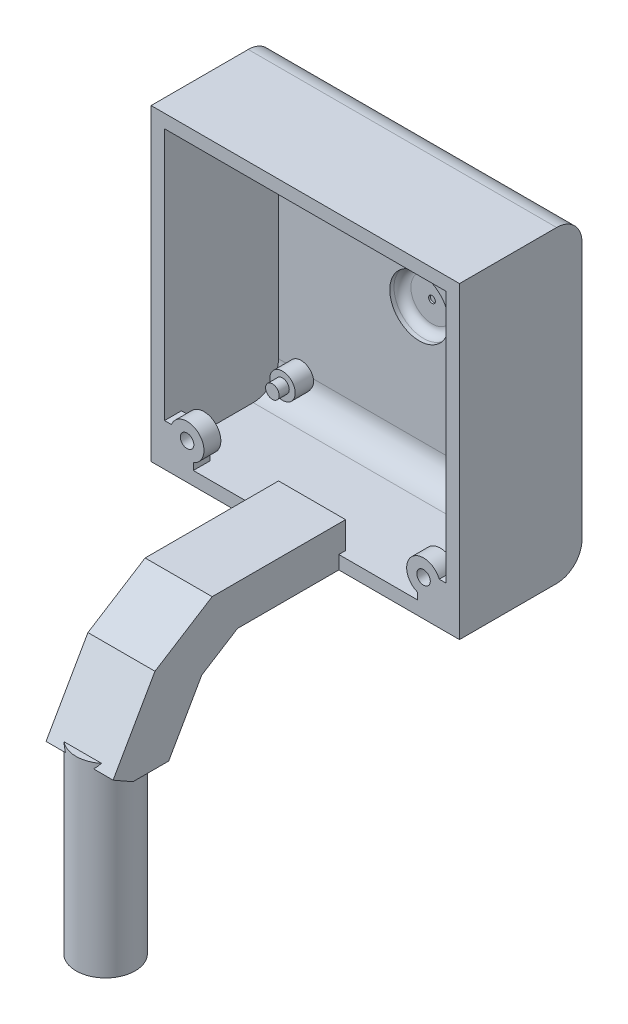
SolidWorks part; units mm, degrees
ref_plane "Front Plane" through (0, 0, 0) normal (0, 0, 1) x (1, 0, 0)
ref_plane "Top Plane" through (0, 0, 0) normal (0, 1, 0) x (1, 0, 0)
ref_plane "Right Plane" through (0, 0, 0) normal (1, 0, 0) x (0, 0, -1)
sketch "Sketch1" plane through (0, 0, 0) normal (0, 0, 1) x (1, 0, 0)
  line L0 (0, 0) -> (0, -36.5125)
  line L1 (0, -36.5125) -> (36.5125, -36.5125)
  line L2 (36.5125, -36.5125) -> (36.5125, 0)
  line L3 (36.5125, 0) -> (0, 0)
  dimension "D1" = 36.5125
extrude "Extrude1" add sketch "Sketch1" along normal blind 1
sketch "Sketch2" plane through (0, 0, 1) normal (0, 0, 1) x (1, 0, 0)
  line L0 (1.5875, -1.5875) -> (34.925, -1.5875)
  line L3 (34.925, -34.925) -> (34.925, -1.5875)
  line L4 (1.5875, -34.925) -> (1.5875, -1.5875)
  line L5 (34.925, -34.925) -> (1.5875, -34.925)
  line L6 (0, 0) -> (36.5125, 0)
  line L7 (36.5125, -36.5125) -> (36.5125, 0) construction
  line L8 (36.5125, 0) -> (0, 0) construction
  line L9 (36.5125, 0) -> (36.5125, -36.5125)
  line L10 (0, -36.5125) -> (36.5125, -36.5125) construction
  line L11 (36.5125, -36.5125) -> (0, -36.5125)
  line L12 (0, 0) -> (0, -36.5125) construction
  line L13 (0, -36.5125) -> (0, 0)
extrude "Extrude2" add sketch "Sketch2" along normal blind 13.5
fillet "Fillet7" radius 3 4 edges at (18.2562, 0, 0) (18.2562, -36.5125, 0) (18.2562, -1.5875, 1) (18.2562, -34.925, 1)
sketch "Sketch5" plane through (0, 0, 1) normal (0, 0, 1) x (1, 0, 0)
  line L0 (1.5875, -1.5875) -> (34.925, -34.925) construction
  line L1 (34.925, -1.5875) -> (1.5875, -34.925) construction
  line L2 (34.925, -34.925) -> (34.925, -1.5875) construction
  circle A0 centre (4.2562, -4.2562) radius 1.5
  circle A1 centre (32.2563, -4.2562) radius 1.5
  circle A2 centre (4.2562, -32.2563) radius 1.5
  circle A3 centre (32.2563, -32.2563) radius 1.5
  point P8 (4.2562, -32.2563)
  point P9 (18.2562, -18.2562)
  point P10 (32.2563, -32.2563)
  point P11 (4.2562, -4.2562)
  point P12 (32.2563, -4.2562)
  dimension "D1" = 14
  dimension "D2" = 14
  dimension "D3" = 14
  dimension "D4" = 14
extrude "Extrude5" add sketch "Sketch5" along normal blind 2.2
sketch "Sketch6" plane through (0, 0, 3.2) normal (0, 0, 1) x (1, 0, 0)
  circle A0 centre (4.2562, -32.2563) radius 0.8
  circle A1 centre (32.2563, -32.2563) radius 0.8
  circle A2 centre (4.2562, -4.2562) radius 0.8
  circle A3 centre (32.2563, -4.2562) radius 0.8
extrude "Extrude6" add sketch "Sketch6" along normal blind 1.2
sketch "Sketch7" plane through (0, 0, 1) normal (0, 0, 1) x (1, 0, 0)
  line L0 (0, 0) -> (36.5125, -36.5125) construction
  line L1 (36.5125, 0) -> (0, -36.5125) construction
  line L2 (0, -36.5125) -> (36.5125, -36.5125) construction
  circle A0 centre (18.2562, -18.2562) radius 4.5
  point P9 (18.2562, -18.2562)
extrude "Extrude7" add sketch "Sketch7" against normal blind 2.5
sketch "Sketch8" plane through (0, 0, 1) normal (0, 0, 1) x (1, 0, 0)
  line L0 (0, 0) -> (36.5125, -36.5125) construction
  line L1 (36.5125, 0) -> (0.5068, -36.3499) construction
  circle A0 centre (18.2562, -18.2562) radius 3.5
  point P6 (18.3431, -18.3431)
extrude "Extrude9" cut sketch "Sketch8" against normal blind 1.5
fillet "Fillet8" radius 1 1 edges at (22.7562, -18.2562, -1.5)
fillet "Fillet10" radius 1 1 edges at (21.7562, -18.2562, -0.5)
sketch "Sketch9" plane through (0, 0, -0.5) normal (0, 0, 1) x (1, 0, 0)
  circle A0 centre (18.2562, -18.2562) radius 0.4
extrude "Extrude10" cut sketch "Sketch9" against normal blind 0.2
sketch "Sketch10" plane through (0, 0, 14.5) normal (0, 0, 1) x (1, 0, 0)
  line L0 (-4.7625, -31.5125) -> (46.0375, -31.5125) construction
  line L1 (5, -15.875) -> (5, -49.2125) construction
  line L2 (31.5125, -15.875) -> (31.5125, -49.2125) construction
  line L3 (31.5125, -34.1128) -> (31.5125, -36.5126)
  line L4 (31.5125, -36.5126) -> (36.5125, -36.5125)
  line L5 (36.5125, -36.5125) -> (36.5125, -31.5125)
  line L6 (36.5125, -36.5125) -> (36.5125, 0) construction
  line L7 (36.5125, -31.5125) -> (34.1128, -31.5125)
  line L8 (2.3997, -31.5125) -> (0, -31.5125)
  line L9 (0, 0) -> (0, -36.5125) construction
  line L10 (0, -31.5125) -> (0, -36.5125)
  line L11 (0, -36.5125) -> (5, -36.5125)
  line L12 (0, -36.5125) -> (36.5125, -36.5125) construction
  line L13 (5, -36.5125) -> (5, -34.1128)
  circle A0 centre (4.2562, -32.2563) radius 2 construction
  circle A1 centre (32.2563, -32.2563) radius 2 construction
  circle A2 centre (4.2562, -32.2563) radius 0.8
  circle A3 centre (32.2563, -32.2563) radius 0.8
  arc A4 (2.3997, -31.5125) -> (5, -34.1128) centre (4.2562, -32.2563) cw
  arc A5 (34.1128, -31.5125) -> (31.5125, -34.1128) centre (32.2563, -32.2563) ccw
  dimension "D1" = 5
  dimension "D2" = 5
  dimension "D3" = 5
extrude "Extrude11" add sketch "Sketch10" against normal blind 2
sketch "Sketch11" plane through (0, 0, 14.5) normal (0, 0, 1) x (1, 0, 0)
  line L0 (14.2875, -36.5125) -> (14.2875, -31.75)
  line L1 (14.2875, -31.75) -> (22.225, -31.75)
  line L2 (22.225, -31.75) -> (22.225, -36.5125)
  line L3 (0, -36.5125) -> (31.5125, -36.5125) construction
  line L4 (22.225, -36.5125) -> (14.2875, -36.5125)
  line L5 (15.875, -33.3375) -> (20.6375, -33.3375)
  line L6 (20.6375, -33.3375) -> (20.6375, -34.925)
  line L7 (34.925, -34.925) -> (1.5875, -34.925) construction
  line L8 (20.6375, -34.925) -> (15.875, -34.925)
  line L9 (5, -34.925) -> (31.5125, -34.925) construction
  line L10 (15.875, -33.3375) -> (15.875, -34.925)
  point P0 (4.2562, -32.2563)
  point P1 (32.2563, -32.2563)
extrude "Extrude12" add sketch "Sketch11" along normal blind 15 and the other way blind 0.8
sketch "Sketch12" plane through (14.2875, 0, 0) normal (-1, 0, 0) x (0, 0, 1)
  line L0 (29.5, -36.5125) -> (29.5, -31.75)
  line L1 (29.5, -31.75) -> (26.5, -36.5125)
  line L2 (26.5, -36.5125) -> (29.5, -36.5125)
  line L3 (14.5, -36.5125) -> (29.5, -36.5125) construction
extrude "Extrude13" cut sketch "Sketch12" against normal through all
sketch "Sketch13" plane through (0, -22.3232, 35.4381) normal (0, -0.533, 0.8461) x (1, 0, 0)
  line L0 (14.2875, -11.1412) -> (22.225, -11.1412)
  line L3 (14.2875, -11.1412) -> (14.2875, -16.7698) construction
  line L6 (20.6375, -14.8936) -> (20.6375, -13.0174)
  line L7 (20.6375, -13.0174) -> (15.875, -13.0174)
  line L8 (20.6375, -13.0174) -> (15.875, -13.0174) construction
  line L9 (15.875, -13.0174) -> (15.875, -14.8936)
  line L10 (20.6375, -14.8936) -> (15.875, -14.8936)
  line L14 (22.225, -11.1412) -> (22.225, -16.7698)
  line L15 (22.225, -16.7698) -> (14.2875, -16.7698)
  line L16 (22.225, -16.7698) -> (14.2875, -16.7698) construction
  line L17 (14.2875, -16.7698) -> (14.2875, -11.1412)
extrude "Extrude14" add sketch "Sketch13" along normal blind 8
sketch "Sketch15" plane through (14.2875, 0, 0) normal (-1, 0, 0) x (0, 0, 1)
  line L0 (36.269, -36.0139) -> (30.7306, -39.1774)
  line L1 (33.269, -40.7764) -> (26.5, -36.5125) construction
  line L2 (30.7306, -39.1774) -> (33.269, -40.7764)
  line L3 (33.269, -40.7764) -> (36.269, -36.0139)
extrude "Extrude16" cut sketch "Sketch15" against normal through all
sketch "Sketch16" plane through (0, -42.7747, 24.433) normal (0, -0.8683, 0.496) x (1, 0, 0)
  line L0 (14.2875, 13.6308) -> (22.225, 13.6308)
  line L1 (22.225, 13.6308) -> (22.225, 7.2526)
  line L2 (22.225, 7.2526) -> (22.225, 13.6308) construction
  line L3 (22.225, 7.2526) -> (14.2875, 7.2526)
  line L4 (14.2875, 7.2526) -> (14.2875, 13.6308)
  line L5 (15.875, 11.5047) -> (20.6375, 11.5047)
  line L6 (20.6375, 11.5047) -> (20.6375, 9.3786)
  line L7 (20.6375, 9.3786) -> (15.875, 9.3786)
  line L8 (15.875, 9.3786) -> (15.875, 11.5047)
extrude "Extrude17" add sketch "Sketch16" along normal blind 10
sketch "Sketch18" plane through (22.225, 0, 0) normal (1, 0, 0) x (0, 0, -1)
  line L0 (-30.1625, -46.0375) -> (-39.6875, -46.0375) construction
  line L2 (-35.6905, -47.8607) -> (-34.6491, -46.0375)
  line L3 (-35.6905, -47.8607) -> (-30.7306, -39.1774) construction
  line L4 (-34.6491, -46.0375) -> (-38.8824, -46.0375)
  line L5 (-35.6905, -47.8607) -> (-41.2289, -44.6972) construction
  line L6 (-38.8824, -46.0375) -> (-35.6905, -47.8607)
extrude "Extrude18" cut sketch "Sketch18" against normal through all
sketch "Sketch19" plane through (0, -46.0375, 0) normal (0, -1, 0) x (1, 0, 0)
  line L1 (14.2875, 34.6491) -> (22.225, 34.6491) construction
  circle A0 centre (18.2562, 38.1491) radius 2.2
  circle A1 centre (18.2562, 38.1491) radius 3.5
  point P0 (18.2562, 38.1491)
  dimension "D1" = 3.9688
  dimension "D2" = 3.5
extrude "Extrude19" add sketch "Sketch19" along normal blind 20 and the other way blind 2
